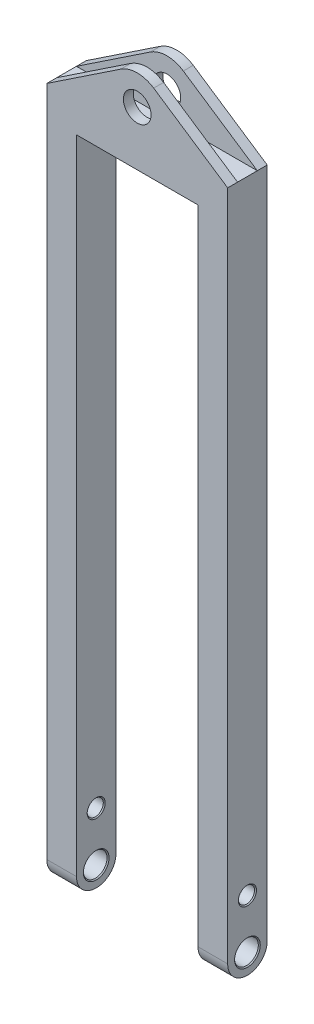
SolidWorks part; units mm, degrees
ref_plane "Płaszczyzna przednia" through (0, 0, 0) normal (0, 0, 1) x (1, 0, 0)
ref_plane "Płaszczyzna górna" through (0, 0, 0) normal (0, 1, 0) x (1, 0, 0)
ref_plane "Płaszczyzna prawa" through (0, 0, 0) normal (1, 0, 0) x (0, 0, -1)
sketch "Szkic1" plane through (0, 0, 0) normal (0, 0, 1) x (1, 0, 0)
  line L1 (0, 0) -> (30, 0)
  line L2 (0, 0) -> (0, 700)
  line L3 (0, 700) -> (30, 700)
  line L4 (30, 0) -> (30, 670)
  line L5 (30, 700) -> (110, 700)
  line L7 (30, 670) -> (153, 670)
  line L9 (110, 700) -> (183, 700)
  line L10 (153, 670) -> (153, 0)
  line L11 (153, 0) -> (183, 0)
  line L12 (183, 700) -> (183, 0)
  dimension "D1" = 123
  dimension "D2" = 700
  dimension "D3" = 30
  dimension "D4" = 30
  dimension "D5" = 30
extrude "Dodanie-wyciągnięcie1" add sketch "Szkic1" along normal blind 40
fillet "Zaokrąglenie1" radius 20 4 edges at (168, 0, 0) (168, 0, 40) (15, 0, 0) (15, 0, 40)
sketch "Szkic2" plane through (0, 0, 0) normal (-1, 0, 0) x (0, 0, 1)
  line L0 (0, 0) -> (20, 0) construction
  line L1 (20, 0) -> (20, 20) construction
  circle A0 centre (20, 20) radius 12
  dimension "D1" = 24
extrude "Wytnij-wyciągnięcie1" cut sketch "Szkic2" against normal through all
sketch "Szkic3" plane through (183, 0, 0) normal (1, 0, 0) x (0, 0, -1)
  line L0 (-20, 20) -> (-20, 70) construction
  circle A0 centre (-20, 70) radius 8.15
  dimension "D1" = 50
extrude "Wytnij-wyciągnięcie2" cut sketch "Szkic3" against normal through all
sketch "Szkic4" plane through (153, 0, 0) normal (-1, 0, 0) x (0, 0, 1)
  line L0 (20, 670) -> (20, 657.5) construction
  line L1 (40, 670) -> (0, 670) construction
  line L2 (20, 657.5) -> (20, 597.5) construction
  line L3 (20, 597.5) -> (20, 537.5) construction
  line L4 (20, 537.5) -> (20, 477.5) construction
  line L5 (20, 477.5) -> (20, 417.5) construction
  circle A0 centre (20, 657.5) radius 1.65
  circle A1 centre (20, 597.5) radius 1.65
  circle A2 centre (20, 537.5) radius 1.65
  circle A3 centre (20, 477.5) radius 1.65
  circle A4 centre (20, 417.5) radius 1.65
  dimension "D2" = 60
  dimension "D6" = 3.3
  dimension "D1" = 12.5
  dimension "D3" = 60
  dimension "D4" = 60
  dimension "D5" = 60
sketch "Szkic5" plane through (0, 0, 0) normal (0, 0, -1) x (-1, 0, 0)
  line L0 (-183, 700) -> (0, 700)
  line L1 (-91.5, 700) -> (-91.5, 761.0679) construction
  line L2 (-74.8462, 749.953) -> (0, 700)
  line L3 (-183, 700) -> (-108.1538, 749.953)
  arc A0 (-108.1538, 749.953) -> (-74.8462, 749.953) centre (-91.5, 725) cw
  circle A1 centre (-91.5, 725) radius 14
  dimension "D1" = 30
  dimension "D2" = 25
extrude "Dodanie-wyciągnięcie2" add sketch "Szkic5" against normal blind 40
sketch "Szkic6" plane through (183, 0, 0) normal (1, 0, 0) x (0, 0, -1)
  line L0 (-40, 700) -> (0, 700) construction
  line L1 (-30, 700) -> (-10, 700)
  line L2 (-30, 700) -> (-30, 755)
  line L3 (-30, 755) -> (-10, 755)
  line L4 (-10, 700) -> (-10, 755)
  line L5 (0, 755) -> (-40, 755) construction
  line L6 (-40, 749.953) -> (-40, 700) construction
  dimension "D1" = 10
  dimension "D2" = 20
extrude "Wytnij-wyciągnięcie4" cut sketch "Szkic6" against normal through all
extrude "Wytnij-wyciągnięcie5" cut sketch "Szkic4" against normal blind 10
cosmetic thread "Oznaczenie gwintu6" parameters "D1"=7, "D2"=4
cosmetic thread "Oznaczenie gwintu7" parameters "D1"=7, "D2"=4
cosmetic thread "Oznaczenie gwintu8" parameters "D1"=7, "D2"=4
cosmetic thread "Oznaczenie gwintu9" parameters "D1"=7, "D2"=4
cosmetic thread "Oznaczenie gwintu10" parameters "D1"=7, "D2"=4
chamfer "Sfazowanie1" distance 0.5 5 edges at (153, 415.85, 20) (153, 475.85, 20) (153, 535.85, 20) (153, 595.85, 20) (153, 655.85, 20)
chamfer "Sfazowanie2" distance 1 angle 45 8 edges at (0, 78.15, 20) (183, 78.15, 20) (153, 78.15, 20) (183, 20, 32) (153, 32, 20) (30, 20, 32) (30, 70, 28.15) (0, 20, 32)
